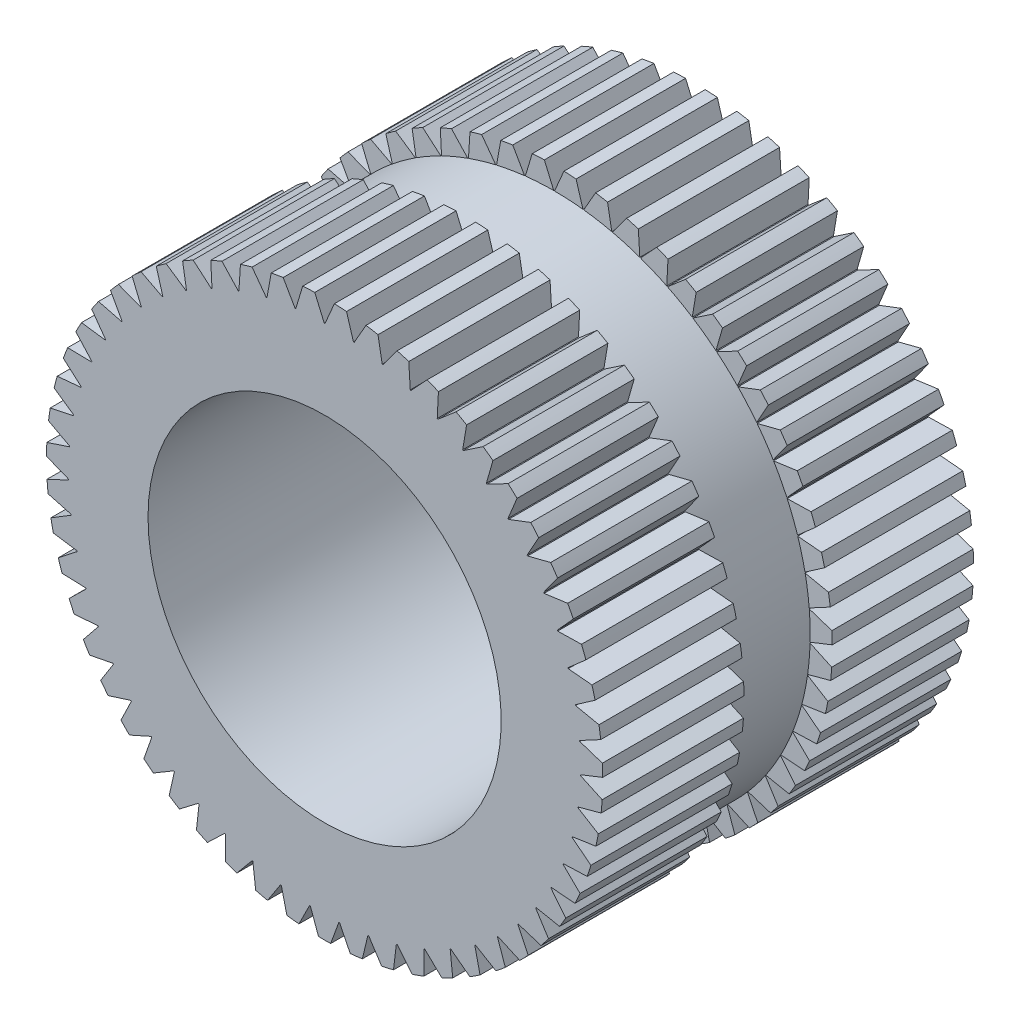
SolidWorks part; units mm, degrees
material "Brass"
ref_plane "Front Plane" through (0, 0, 0) normal (0, 0, 1) x (1, 0, 0)
ref_plane "Top Plane" through (0, 0, 0) normal (0, 1, 0) x (1, 0, 0)
ref_plane "Right Plane" through (0, 0, 0) normal (1, 0, 0) x (0, 0, -1)
ref_plane "Plane1" through (0, 0, 2.1) normal (0, 0, 1) x (1, 0, 0)
sketch "Sketch1" plane through (0, 0, 2.1) normal (0, 0, 1) x (1, 0, 0)
  line L0 (-2.8431, 0.5717) -> (-3.1074, 0.5164)
  line L1 (-3.127, 0.38) -> (-2.889, 0.2525)
  line L2 (-2.8897, 0.2438) -> (-3.146, 0.1588)
  line L3 (-3.1499, 0.0211) -> (-2.8989, -0.0785)
  line L4 (-2.8987, -0.0872) -> (-3.1436, -0.2009)
  line L5 (-3.1318, -0.3381) -> (-2.8711, -0.4084)
  line L6 (-2.8699, -0.417) -> (-3.1002, -0.5579)
  line L7 (-3.0728, -0.6929) -> (-2.8058, -0.733)
  line L8 (-2.8036, -0.7414) -> (-3.0164, -0.9077)
  line L9 (-2.9738, -1.0387) -> (-2.704, -1.0481)
  line L10 (-2.7008, -1.0562) -> (-2.8933, -1.2456)
  line L11 (-2.836, -1.3709) -> (-2.5669, -1.3495)
  line L12 (-2.5628, -1.3572) -> (-2.7324, -1.5673)
  line L13 (-2.6613, -1.6852) -> (-2.3963, -1.6333)
  line L14 (-2.3914, -1.6405) -> (-2.536, -1.8685)
  line L15 (-2.4518, -1.9776) -> (-2.1945, -1.8958)
  line L16 (-2.1888, -1.9024) -> (-2.3064, -2.1454)
  line L17 (-2.2104, -2.2442) -> (-1.9641, -2.1336)
  line L18 (-1.9577, -2.1395) -> (-2.0468, -2.3944)
  line L19 (-1.9402, -2.4816) -> (-1.7081, -2.3436)
  line L20 (-1.7011, -2.3487) -> (-1.7605, -2.6121)
  line L21 (-1.6447, -2.6865) -> (-1.4298, -2.523)
  line L22 (-1.4222, -2.5273) -> (-1.4513, -2.7957)
  line L23 (-1.3277, -2.8565) -> (-1.1329, -2.6696)
  line L24 (-1.1249, -2.6729) -> (-1.1232, -2.943)
  line L25 (-0.9934, -2.9892) -> (-0.8212, -2.7813)
  line L26 (-0.8129, -2.7838) -> (-0.7804, -3.0518)
  line L27 (-0.6462, -3.083) -> (-0.4988, -2.8568)
  line L28 (-0.4902, -2.8583) -> (-0.4274, -3.1209)
  line L29 (-0.2906, -3.1366) -> (-0.1699, -2.895)
  line L30 (-0.1612, -2.8955) -> (-0.0689, -3.1492)
  line L31 (0.0689, -3.1492) -> (0.1612, -2.8955)
  line L32 (0.1699, -2.895) -> (0.2906, -3.1366)
  line L33 (0.4274, -3.1209) -> (0.4902, -2.8583)
  line L34 (0.4988, -2.8568) -> (0.6462, -3.083)
  line L35 (0.7804, -3.0518) -> (0.8129, -2.7838)
  line L36 (0.8212, -2.7813) -> (0.9934, -2.9892)
  line L37 (1.1232, -2.943) -> (1.1249, -2.6729)
  line L38 (1.1329, -2.6696) -> (1.3277, -2.8565)
  line L39 (1.4513, -2.7957) -> (1.4222, -2.5273)
  line L40 (1.4298, -2.523) -> (1.6447, -2.6865)
  line L41 (1.7605, -2.6121) -> (1.7011, -2.3487)
  line L42 (1.7081, -2.3436) -> (1.9402, -2.4816)
  line L43 (2.0468, -2.3944) -> (1.9577, -2.1395)
  line L44 (1.9641, -2.1336) -> (2.2104, -2.2442)
  line L45 (2.3064, -2.1454) -> (2.1888, -1.9024)
  line L46 (2.1945, -1.8958) -> (2.4518, -1.9776)
  line L47 (2.536, -1.8685) -> (2.3914, -1.6405)
  line L48 (2.3963, -1.6333) -> (2.6613, -1.6852)
  line L49 (2.7324, -1.5673) -> (2.5628, -1.3572)
  line L50 (2.5669, -1.3495) -> (2.836, -1.3709)
  line L51 (2.8933, -1.2456) -> (2.7008, -1.0562)
  line L52 (2.704, -1.0481) -> (2.9738, -1.0387)
  line L53 (3.0164, -0.9077) -> (2.8036, -0.7414)
  line L54 (2.8058, -0.733) -> (3.0728, -0.6929)
  line L55 (3.1002, -0.5579) -> (2.8699, -0.417)
  line L56 (2.8711, -0.4084) -> (3.1318, -0.3381)
  line L57 (3.1436, -0.2009) -> (2.8987, -0.0872)
  line L58 (2.8989, -0.0785) -> (3.1499, 0.0211)
  line L59 (3.146, 0.1588) -> (2.8897, 0.2438)
  line L60 (2.889, 0.2525) -> (3.127, 0.38)
  line L61 (3.1074, 0.5164) -> (2.8431, 0.5717)
  line L62 (2.8414, 0.5802) -> (3.0633, 0.734)
  line L63 (3.0283, 0.8672) -> (2.7594, 0.892)
  line L64 (2.7567, 0.9003) -> (2.9597, 1.0784)
  line L65 (2.9097, 1.2067) -> (2.6397, 1.2008)
  line L66 (2.6361, 1.2087) -> (2.8174, 1.4087)
  line L67 (2.7532, 1.5306) -> (2.4857, 1.4938)
  line L68 (2.4812, 1.5013) -> (2.6385, 1.7207)
  line L69 (2.5607, 1.8344) -> (2.2992, 1.7674)
  line L70 (2.2939, 1.7743) -> (2.4251, 2.0103)
  line L71 (2.3349, 2.1144) -> (2.0827, 2.018)
  line L72 (2.0767, 2.0242) -> (2.1802, 2.2736)
  line L73 (2.0787, 2.3667) -> (1.8391, 2.2423)
  line L74 (1.8324, 2.2478) -> (1.9068, 2.5073)
  line L75 (1.7954, 2.5883) -> (1.5715, 2.4373)
  line L76 (1.5642, 2.442) -> (1.6086, 2.7083)
  line L77 (1.4886, 2.7761) -> (1.2834, 2.6005)
  line L78 (1.2756, 2.6044) -> (1.2893, 2.874)
  line L79 (1.1625, 2.9277) -> (0.9786, 2.7299)
  line L80 (0.9705, 2.7328) -> (0.9533, 3.0023)
  line L81 (0.8212, 3.0411) -> (0.6611, 2.8236)
  line L82 (0.6526, 2.8256) -> (0.6049, 3.0914)
  line L83 (0.4692, 3.1149) -> (0.3349, 2.8806)
  line L84 (0.3263, 2.8816) -> (0.2485, 3.1402)
  line L85 (0.111, 3.148) -> (0.0043, 2.9)
  line L86 (-0.0043, 2.9) -> (-0.111, 3.148)
  line L87 (-0.2485, 3.1402) -> (-0.3263, 2.8816)
  line L88 (-0.3349, 2.8806) -> (-0.4692, 3.1149)
  line L89 (-0.6049, 3.0914) -> (-0.6526, 2.8256)
  line L90 (-0.6611, 2.8236) -> (-0.8212, 3.0411)
  line L91 (-0.9533, 3.0023) -> (-0.9705, 2.7328)
  line L92 (-0.9786, 2.7299) -> (-1.1625, 2.9277)
  line L93 (-1.2893, 2.874) -> (-1.2756, 2.6044)
  line L94 (-1.2834, 2.6005) -> (-1.4886, 2.7761)
  line L95 (-1.6086, 2.7083) -> (-1.5642, 2.442)
  line L96 (-1.5715, 2.4373) -> (-1.7954, 2.5883)
  line L97 (-1.9068, 2.5073) -> (-1.8324, 2.2478)
  line L98 (-1.8391, 2.2423) -> (-2.0787, 2.3667)
  line L99 (-2.1802, 2.2736) -> (-2.0767, 2.0242)
  line L100 (-2.0827, 2.018) -> (-2.3349, 2.1144)
  line L101 (-2.4251, 2.0103) -> (-2.2939, 1.7743)
  line L102 (-2.2992, 1.7674) -> (-2.5607, 1.8344)
  line L103 (-2.6385, 1.7207) -> (-2.4812, 1.5013)
  line L104 (-2.4857, 1.4938) -> (-2.7532, 1.5306)
  line L105 (-2.8174, 1.4087) -> (-2.6361, 1.2087)
  line L106 (-2.6397, 1.2008) -> (-2.9097, 1.2067)
  line L107 (-2.9597, 1.0784) -> (-2.7567, 0.9003)
  line L108 (-2.7594, 0.892) -> (-3.0283, 0.8672)
  line L109 (-3.0633, 0.734) -> (-2.8414, 0.5802)
  arc A0 (-2.8414, 0.5802) -> (-2.8431, 0.5717) centre (0, 0) ccw
  arc A1 (-3.1074, 0.5164) -> (-3.127, 0.38) centre (0, 0) ccw
  arc A2 (-2.889, 0.2525) -> (-2.8897, 0.2438) centre (0, 0) ccw
  arc A3 (-3.146, 0.1588) -> (-3.1499, 0.0211) centre (0, 0) ccw
  arc A4 (-2.8989, -0.0785) -> (-2.8987, -0.0872) centre (0, 0) ccw
  arc A5 (-3.1436, -0.2009) -> (-3.1318, -0.3381) centre (0, 0) ccw
  arc A6 (-2.8711, -0.4084) -> (-2.8699, -0.417) centre (0, 0) ccw
  arc A7 (-3.1002, -0.5579) -> (-3.0728, -0.6929) centre (0, 0) ccw
  arc A8 (-2.8058, -0.733) -> (-2.8036, -0.7414) centre (0, 0) ccw
  arc A9 (-3.0164, -0.9077) -> (-2.9738, -1.0387) centre (0, 0) ccw
  arc A10 (-2.704, -1.0481) -> (-2.7008, -1.0562) centre (0, 0) ccw
  arc A11 (-2.8933, -1.2456) -> (-2.836, -1.3709) centre (0, 0) ccw
  arc A12 (-2.5669, -1.3495) -> (-2.5628, -1.3572) centre (0, 0) ccw
  arc A13 (-2.7324, -1.5673) -> (-2.6613, -1.6852) centre (0, 0) ccw
  arc A14 (-2.3963, -1.6333) -> (-2.3914, -1.6405) centre (0, 0) ccw
  arc A15 (-2.536, -1.8685) -> (-2.4518, -1.9776) centre (0, 0) ccw
  arc A16 (-2.1945, -1.8958) -> (-2.1888, -1.9024) centre (0, 0) ccw
  arc A17 (-2.3064, -2.1454) -> (-2.2104, -2.2442) centre (0, 0) ccw
  arc A18 (-1.9641, -2.1336) -> (-1.9577, -2.1395) centre (0, 0) ccw
  arc A19 (-2.0468, -2.3944) -> (-1.9402, -2.4816) centre (0, 0) ccw
  arc A20 (-1.7081, -2.3436) -> (-1.7011, -2.3487) centre (0, 0) ccw
  arc A21 (-1.7605, -2.6121) -> (-1.6447, -2.6865) centre (0, 0) ccw
  arc A22 (-1.4298, -2.523) -> (-1.4222, -2.5273) centre (0, 0) ccw
  arc A23 (-1.4513, -2.7957) -> (-1.3277, -2.8565) centre (0, 0) ccw
  arc A24 (-1.1329, -2.6696) -> (-1.1249, -2.6729) centre (0, 0) ccw
  arc A25 (-1.1232, -2.943) -> (-0.9934, -2.9892) centre (0, 0) ccw
  arc A26 (-0.8212, -2.7813) -> (-0.8129, -2.7838) centre (0, 0) ccw
  arc A27 (-0.7804, -3.0518) -> (-0.6462, -3.083) centre (0, 0) ccw
  arc A28 (-0.4988, -2.8568) -> (-0.4902, -2.8583) centre (0, 0) ccw
  arc A29 (-0.4274, -3.1209) -> (-0.2906, -3.1366) centre (0, 0) ccw
  arc A30 (-0.1699, -2.895) -> (-0.1612, -2.8955) centre (0, 0) ccw
  arc A31 (-0.0689, -3.1492) -> (0.0689, -3.1492) centre (0, 0) ccw
  arc A32 (0.1612, -2.8955) -> (0.1699, -2.895) centre (0, 0) ccw
  arc A33 (0.2906, -3.1366) -> (0.4274, -3.1209) centre (0, 0) ccw
  arc A34 (0.4902, -2.8583) -> (0.4988, -2.8568) centre (0, 0) ccw
  arc A35 (0.6462, -3.083) -> (0.7804, -3.0518) centre (0, 0) ccw
  arc A36 (0.8129, -2.7838) -> (0.8212, -2.7813) centre (0, 0) ccw
  arc A37 (0.9934, -2.9892) -> (1.1232, -2.943) centre (0, 0) ccw
  arc A38 (1.1249, -2.6729) -> (1.1329, -2.6696) centre (0, 0) ccw
  arc A39 (1.3277, -2.8565) -> (1.4513, -2.7957) centre (0, 0) ccw
  arc A40 (1.4222, -2.5273) -> (1.4298, -2.523) centre (0, 0) ccw
  arc A41 (1.6447, -2.6865) -> (1.7605, -2.6121) centre (0, 0) ccw
  arc A42 (1.7011, -2.3487) -> (1.7081, -2.3436) centre (0, 0) ccw
  arc A43 (1.9402, -2.4816) -> (2.0468, -2.3944) centre (0, 0) ccw
  arc A44 (1.9577, -2.1395) -> (1.9641, -2.1336) centre (0, 0) ccw
  arc A45 (2.2104, -2.2442) -> (2.3064, -2.1454) centre (0, 0) ccw
  arc A46 (2.1888, -1.9024) -> (2.1945, -1.8958) centre (0, 0) ccw
  arc A47 (2.4518, -1.9776) -> (2.536, -1.8685) centre (0, 0) ccw
  arc A48 (2.3914, -1.6405) -> (2.3963, -1.6333) centre (0, 0) ccw
  arc A49 (2.6613, -1.6852) -> (2.7324, -1.5673) centre (0, 0) ccw
  arc A50 (2.5628, -1.3572) -> (2.5669, -1.3495) centre (0, 0) ccw
  arc A51 (2.836, -1.3709) -> (2.8933, -1.2456) centre (0, 0) ccw
  arc A52 (2.7008, -1.0562) -> (2.704, -1.0481) centre (0, 0) ccw
  arc A53 (2.9738, -1.0387) -> (3.0164, -0.9077) centre (0, 0) ccw
  arc A54 (2.8036, -0.7414) -> (2.8058, -0.733) centre (0, 0) ccw
  arc A55 (3.0728, -0.6929) -> (3.1002, -0.5579) centre (0, 0) ccw
  arc A56 (2.8699, -0.417) -> (2.8711, -0.4084) centre (0, 0) ccw
  arc A57 (3.1318, -0.3381) -> (3.1436, -0.2009) centre (0, 0) ccw
  arc A58 (2.8987, -0.0872) -> (2.8989, -0.0785) centre (0, 0) ccw
  arc A59 (3.1499, 0.0211) -> (3.146, 0.1588) centre (0, 0) ccw
  arc A60 (2.8897, 0.2438) -> (2.889, 0.2525) centre (0, 0) ccw
  arc A61 (3.127, 0.38) -> (3.1074, 0.5164) centre (0, 0) ccw
  arc A62 (2.8431, 0.5717) -> (2.8414, 0.5802) centre (0, 0) ccw
  arc A63 (3.0633, 0.734) -> (3.0283, 0.8672) centre (0, 0) ccw
  arc A64 (2.7594, 0.892) -> (2.7567, 0.9003) centre (0, 0) ccw
  arc A65 (2.9597, 1.0784) -> (2.9097, 1.2067) centre (0, 0) ccw
  arc A66 (2.6397, 1.2008) -> (2.6361, 1.2087) centre (0, 0) ccw
  arc A67 (2.8174, 1.4087) -> (2.7532, 1.5306) centre (0, 0) ccw
  arc A68 (2.4857, 1.4938) -> (2.4812, 1.5013) centre (0, 0) ccw
  arc A69 (2.6385, 1.7207) -> (2.5607, 1.8344) centre (0, 0) ccw
  arc A70 (2.2992, 1.7674) -> (2.2939, 1.7743) centre (0, 0) ccw
  arc A71 (2.4251, 2.0103) -> (2.3349, 2.1144) centre (0, 0) ccw
  arc A72 (2.0827, 2.018) -> (2.0767, 2.0242) centre (0, 0) ccw
  arc A73 (2.1802, 2.2736) -> (2.0787, 2.3667) centre (0, 0) ccw
  arc A74 (1.8391, 2.2423) -> (1.8324, 2.2478) centre (0, 0) ccw
  arc A75 (1.9068, 2.5073) -> (1.7954, 2.5883) centre (0, 0) ccw
  arc A76 (1.5715, 2.4373) -> (1.5642, 2.442) centre (0, 0) ccw
  arc A77 (1.6086, 2.7083) -> (1.4886, 2.7761) centre (0, 0) ccw
  arc A78 (1.2834, 2.6005) -> (1.2756, 2.6044) centre (0, 0) ccw
  arc A79 (1.2893, 2.874) -> (1.1625, 2.9277) centre (0, 0) ccw
  arc A80 (0.9786, 2.7299) -> (0.9705, 2.7328) centre (0, 0) ccw
  arc A81 (0.9533, 3.0023) -> (0.8212, 3.0411) centre (0, 0) ccw
  arc A82 (0.6611, 2.8236) -> (0.6526, 2.8256) centre (0, 0) ccw
  arc A83 (0.6049, 3.0914) -> (0.4692, 3.1149) centre (0, 0) ccw
  arc A84 (0.3349, 2.8806) -> (0.3263, 2.8816) centre (0, 0) ccw
  arc A85 (0.2485, 3.1402) -> (0.111, 3.148) centre (0, 0) ccw
  arc A86 (0.0043, 2.9) -> (-0.0043, 2.9) centre (0, 0) ccw
  arc A87 (-0.111, 3.148) -> (-0.2485, 3.1402) centre (0, 0) ccw
  arc A88 (-0.3263, 2.8816) -> (-0.3349, 2.8806) centre (0, 0) ccw
  arc A89 (-0.4692, 3.1149) -> (-0.6049, 3.0914) centre (0, 0) ccw
  arc A90 (-0.6526, 2.8256) -> (-0.6611, 2.8236) centre (0, 0) ccw
  arc A91 (-0.8212, 3.0411) -> (-0.9533, 3.0023) centre (0, 0) ccw
  arc A92 (-0.9705, 2.7328) -> (-0.9786, 2.7299) centre (0, 0) ccw
  arc A93 (-1.1625, 2.9277) -> (-1.2893, 2.874) centre (0, 0) ccw
  arc A94 (-1.2756, 2.6044) -> (-1.2834, 2.6005) centre (0, 0) ccw
  arc A95 (-1.4886, 2.7761) -> (-1.6086, 2.7083) centre (0, 0) ccw
  arc A96 (-1.5642, 2.442) -> (-1.5715, 2.4373) centre (0, 0) ccw
  arc A97 (-1.7954, 2.5883) -> (-1.9068, 2.5073) centre (0, 0) ccw
  arc A98 (-1.8324, 2.2478) -> (-1.8391, 2.2423) centre (0, 0) ccw
  arc A99 (-2.0787, 2.3667) -> (-2.1802, 2.2736) centre (0, 0) ccw
  arc A100 (-2.0767, 2.0242) -> (-2.0827, 2.018) centre (0, 0) ccw
  arc A101 (-2.3349, 2.1144) -> (-2.4251, 2.0103) centre (0, 0) ccw
  arc A102 (-2.2939, 1.7743) -> (-2.2992, 1.7674) centre (0, 0) ccw
  arc A103 (-2.5607, 1.8344) -> (-2.6385, 1.7207) centre (0, 0) ccw
  arc A104 (-2.4812, 1.5013) -> (-2.4857, 1.4938) centre (0, 0) ccw
  arc A105 (-2.7532, 1.5306) -> (-2.8174, 1.4087) centre (0, 0) ccw
  arc A106 (-2.6361, 1.2087) -> (-2.6397, 1.2008) centre (0, 0) ccw
  arc A107 (-2.9097, 1.2067) -> (-2.9597, 1.0784) centre (0, 0) ccw
  arc A108 (-2.7567, 0.9003) -> (-2.7594, 0.892) centre (0, 0) ccw
  arc A109 (-3.0283, 0.8672) -> (-3.0633, 0.734) centre (0, 0) ccw
extrude "Boss-Extrude1" add sketch "Sketch1" against normal blind 1.6
sketch "Sketch2" plane through (0, 0, 0.5) normal (0, 0, -1) x (-1, 0, 0)
  circle A0 centre (0, 0) radius 2.9
extrude "Boss-Extrude2" add sketch "Sketch2" along normal blind 1
sketch "Sketch3" plane through (0, 0, -0.5) normal (0, 0, -1) x (-1, 0, 0)
  line L0 (2.6397, 1.2008) -> (2.9097, 1.2067)
  line L1 (2.9597, 1.0784) -> (2.7567, 0.9003)
  line L2 (2.7594, 0.892) -> (3.0283, 0.8672)
  line L3 (3.0633, 0.734) -> (2.8414, 0.5802)
  line L4 (2.8431, 0.5717) -> (3.1074, 0.5164)
  line L5 (3.127, 0.38) -> (2.889, 0.2525)
  line L6 (2.8897, 0.2438) -> (3.146, 0.1588)
  line L7 (3.1499, 0.0211) -> (2.8989, -0.0785)
  line L8 (2.8987, -0.0872) -> (3.1436, -0.2009)
  line L9 (3.1318, -0.3381) -> (2.8711, -0.4084)
  line L10 (2.8699, -0.417) -> (3.1002, -0.5579)
  line L11 (3.0728, -0.6929) -> (2.8058, -0.733)
  line L12 (2.8036, -0.7414) -> (3.0164, -0.9077)
  line L13 (2.9738, -1.0387) -> (2.704, -1.0481)
  line L14 (2.7008, -1.0562) -> (2.8933, -1.2456)
  line L15 (2.836, -1.3709) -> (2.5669, -1.3495)
  line L16 (2.5628, -1.3572) -> (2.7324, -1.5673)
  line L17 (2.6613, -1.6852) -> (2.3963, -1.6333)
  line L18 (2.3914, -1.6405) -> (2.536, -1.8685)
  line L19 (2.4518, -1.9776) -> (2.1945, -1.8958)
  line L20 (2.1888, -1.9024) -> (2.3064, -2.1454)
  line L21 (2.2104, -2.2442) -> (1.9641, -2.1336)
  line L22 (1.9577, -2.1395) -> (2.0468, -2.3944)
  line L23 (1.9402, -2.4816) -> (1.7081, -2.3436)
  line L24 (1.7011, -2.3487) -> (1.7605, -2.6121)
  line L25 (1.6447, -2.6865) -> (1.4298, -2.523)
  line L26 (1.4222, -2.5273) -> (1.4513, -2.7957)
  line L27 (1.3277, -2.8565) -> (1.1329, -2.6696)
  line L28 (1.1249, -2.6729) -> (1.1232, -2.943)
  line L29 (0.9934, -2.9892) -> (0.8212, -2.7813)
  line L30 (0.8129, -2.7838) -> (0.7804, -3.0518)
  line L31 (0.6462, -3.083) -> (0.4988, -2.8568)
  line L32 (0.4902, -2.8583) -> (0.4274, -3.1209)
  line L33 (0.2906, -3.1366) -> (0.1699, -2.895)
  line L34 (0.1612, -2.8955) -> (0.0689, -3.1492)
  line L35 (-0.0689, -3.1492) -> (-0.1612, -2.8955)
  line L36 (-0.1699, -2.895) -> (-0.2906, -3.1366)
  line L37 (-0.4274, -3.1209) -> (-0.4902, -2.8583)
  line L38 (-0.4988, -2.8568) -> (-0.6462, -3.083)
  line L39 (-0.7804, -3.0518) -> (-0.8129, -2.7838)
  line L40 (-0.8212, -2.7813) -> (-0.9934, -2.9892)
  line L41 (-1.1232, -2.943) -> (-1.1249, -2.6729)
  line L42 (-1.1329, -2.6696) -> (-1.3277, -2.8565)
  line L43 (-1.4513, -2.7957) -> (-1.4222, -2.5273)
  line L44 (-1.4298, -2.523) -> (-1.6447, -2.6865)
  line L45 (-1.7605, -2.6121) -> (-1.7011, -2.3487)
  line L46 (-1.7081, -2.3436) -> (-1.9402, -2.4816)
  line L47 (-2.0468, -2.3944) -> (-1.9577, -2.1395)
  line L48 (-1.9641, -2.1336) -> (-2.2104, -2.2442)
  line L49 (-2.3064, -2.1454) -> (-2.1888, -1.9024)
  line L50 (-2.1945, -1.8958) -> (-2.4518, -1.9776)
  line L51 (-2.536, -1.8685) -> (-2.3914, -1.6405)
  line L52 (-2.3963, -1.6333) -> (-2.6613, -1.6852)
  line L53 (-2.7324, -1.5673) -> (-2.5628, -1.3572)
  line L54 (-2.5669, -1.3495) -> (-2.836, -1.3709)
  line L55 (-2.8933, -1.2456) -> (-2.7008, -1.0562)
  line L56 (-2.704, -1.0481) -> (-2.9738, -1.0387)
  line L57 (-3.0164, -0.9077) -> (-2.8036, -0.7414)
  line L58 (-2.8058, -0.733) -> (-3.0728, -0.6929)
  line L59 (-3.1002, -0.5579) -> (-2.8699, -0.417)
  line L60 (-2.8711, -0.4084) -> (-3.1318, -0.3381)
  line L61 (-3.1436, -0.2009) -> (-2.8987, -0.0872)
  line L62 (-2.8989, -0.0785) -> (-3.1499, 0.0211)
  line L63 (-3.146, 0.1588) -> (-2.8897, 0.2438)
  line L64 (-2.889, 0.2525) -> (-3.127, 0.38)
  line L65 (-3.1074, 0.5164) -> (-2.8431, 0.5717)
  line L66 (-2.8414, 0.5802) -> (-3.0633, 0.734)
  line L67 (-3.0283, 0.8672) -> (-2.7594, 0.892)
  line L68 (-2.7567, 0.9003) -> (-2.9597, 1.0784)
  line L69 (-2.9097, 1.2067) -> (-2.6397, 1.2008)
  line L70 (-2.6361, 1.2087) -> (-2.8174, 1.4087)
  line L71 (-2.7532, 1.5306) -> (-2.4857, 1.4938)
  line L72 (-2.4812, 1.5013) -> (-2.6385, 1.7207)
  line L73 (-2.5607, 1.8344) -> (-2.2992, 1.7674)
  line L74 (-2.2939, 1.7743) -> (-2.4251, 2.0103)
  line L75 (-2.3349, 2.1144) -> (-2.0827, 2.018)
  line L76 (-2.0767, 2.0242) -> (-2.1802, 2.2736)
  line L77 (-2.0787, 2.3667) -> (-1.8391, 2.2423)
  line L78 (-1.8324, 2.2478) -> (-1.9068, 2.5073)
  line L79 (-1.7954, 2.5883) -> (-1.5715, 2.4373)
  line L80 (-1.5642, 2.442) -> (-1.6086, 2.7083)
  line L81 (-1.4886, 2.7761) -> (-1.2834, 2.6005)
  line L82 (-1.2756, 2.6044) -> (-1.2893, 2.874)
  line L83 (-1.1625, 2.9277) -> (-0.9786, 2.7299)
  line L84 (-0.9705, 2.7328) -> (-0.9533, 3.0023)
  line L85 (-0.8212, 3.0411) -> (-0.6611, 2.8236)
  line L86 (-0.6526, 2.8256) -> (-0.6049, 3.0914)
  line L87 (-0.4692, 3.1149) -> (-0.3349, 2.8806)
  line L88 (-0.3263, 2.8816) -> (-0.2485, 3.1402)
  line L89 (-0.111, 3.148) -> (-0.0043, 2.9)
  line L90 (0.0043, 2.9) -> (0.111, 3.148)
  line L91 (0.2485, 3.1402) -> (0.3263, 2.8816)
  line L92 (0.3349, 2.8806) -> (0.4692, 3.1149)
  line L93 (0.6049, 3.0914) -> (0.6526, 2.8256)
  line L94 (0.6611, 2.8236) -> (0.8212, 3.0411)
  line L95 (0.9533, 3.0023) -> (0.9705, 2.7328)
  line L96 (0.9786, 2.7299) -> (1.1625, 2.9277)
  line L97 (1.2893, 2.874) -> (1.2756, 2.6044)
  line L98 (1.2834, 2.6005) -> (1.4886, 2.7761)
  line L99 (1.6086, 2.7083) -> (1.5642, 2.442)
  line L100 (1.5715, 2.4373) -> (1.7954, 2.5883)
  line L101 (1.9068, 2.5073) -> (1.8324, 2.2478)
  line L102 (1.8391, 2.2423) -> (2.0787, 2.3667)
  line L103 (2.1802, 2.2736) -> (2.0767, 2.0242)
  line L104 (2.0827, 2.018) -> (2.3349, 2.1144)
  line L105 (2.4251, 2.0103) -> (2.2939, 1.7743)
  line L106 (2.2992, 1.7674) -> (2.5607, 1.8344)
  line L107 (2.6385, 1.7207) -> (2.4812, 1.5013)
  line L108 (2.4857, 1.4938) -> (2.7532, 1.5306)
  line L109 (2.8174, 1.4087) -> (2.6361, 1.2087)
  arc A0 (2.6361, 1.2087) -> (2.6397, 1.2008) centre (0, 0) cw
  arc A1 (2.9097, 1.2067) -> (2.9597, 1.0784) centre (0, 0) cw
  arc A2 (2.7567, 0.9003) -> (2.7594, 0.892) centre (0, 0) cw
  arc A3 (3.0283, 0.8672) -> (3.0633, 0.734) centre (0, 0) cw
  arc A4 (2.8414, 0.5802) -> (2.8431, 0.5717) centre (0, 0) cw
  arc A5 (3.1074, 0.5164) -> (3.127, 0.38) centre (0, 0) cw
  arc A6 (2.889, 0.2525) -> (2.8897, 0.2438) centre (0, 0) cw
  arc A7 (3.146, 0.1588) -> (3.1499, 0.0211) centre (0, 0) cw
  arc A8 (2.8989, -0.0785) -> (2.8987, -0.0872) centre (0, 0) cw
  arc A9 (3.1436, -0.2009) -> (3.1318, -0.3381) centre (0, 0) cw
  arc A10 (2.8711, -0.4084) -> (2.8699, -0.417) centre (0, 0) cw
  arc A11 (3.1002, -0.5579) -> (3.0728, -0.6929) centre (0, 0) cw
  arc A12 (2.8058, -0.733) -> (2.8036, -0.7414) centre (0, 0) cw
  arc A13 (3.0164, -0.9077) -> (2.9738, -1.0387) centre (0, 0) cw
  arc A14 (2.704, -1.0481) -> (2.7008, -1.0562) centre (0, 0) cw
  arc A15 (2.8933, -1.2456) -> (2.836, -1.3709) centre (0, 0) cw
  arc A16 (2.5669, -1.3495) -> (2.5628, -1.3572) centre (0, 0) cw
  arc A17 (2.7324, -1.5673) -> (2.6613, -1.6852) centre (0, 0) cw
  arc A18 (2.3963, -1.6333) -> (2.3914, -1.6405) centre (0, 0) cw
  arc A19 (2.536, -1.8685) -> (2.4518, -1.9776) centre (0, 0) cw
  arc A20 (2.1945, -1.8958) -> (2.1888, -1.9024) centre (0, 0) cw
  arc A21 (2.3064, -2.1454) -> (2.2104, -2.2442) centre (0, 0) cw
  arc A22 (1.9641, -2.1336) -> (1.9577, -2.1395) centre (0, 0) cw
  arc A23 (2.0468, -2.3944) -> (1.9402, -2.4816) centre (0, 0) cw
  arc A24 (1.7081, -2.3436) -> (1.7011, -2.3487) centre (0, 0) cw
  arc A25 (1.7605, -2.6121) -> (1.6447, -2.6865) centre (0, 0) cw
  arc A26 (1.4298, -2.523) -> (1.4222, -2.5273) centre (0, 0) cw
  arc A27 (1.4513, -2.7957) -> (1.3277, -2.8565) centre (0, 0) cw
  arc A28 (1.1329, -2.6696) -> (1.1249, -2.6729) centre (0, 0) cw
  arc A29 (1.1232, -2.943) -> (0.9934, -2.9892) centre (0, 0) cw
  arc A30 (0.8212, -2.7813) -> (0.8129, -2.7838) centre (0, 0) cw
  arc A31 (0.7804, -3.0518) -> (0.6462, -3.083) centre (0, 0) cw
  arc A32 (0.4988, -2.8568) -> (0.4902, -2.8583) centre (0, 0) cw
  arc A33 (0.4274, -3.1209) -> (0.2906, -3.1366) centre (0, 0) cw
  arc A34 (0.1699, -2.895) -> (0.1612, -2.8955) centre (0, 0) cw
  arc A35 (0.0689, -3.1492) -> (-0.0689, -3.1492) centre (0, 0) cw
  arc A36 (-0.1612, -2.8955) -> (-0.1699, -2.895) centre (0, 0) cw
  arc A37 (-0.2906, -3.1366) -> (-0.4274, -3.1209) centre (0, 0) cw
  arc A38 (-0.4902, -2.8583) -> (-0.4988, -2.8568) centre (0, 0) cw
  arc A39 (-0.6462, -3.083) -> (-0.7804, -3.0518) centre (0, 0) cw
  arc A40 (-0.8129, -2.7838) -> (-0.8212, -2.7813) centre (0, 0) cw
  arc A41 (-0.9934, -2.9892) -> (-1.1232, -2.943) centre (0, 0) cw
  arc A42 (-1.1249, -2.6729) -> (-1.1329, -2.6696) centre (0, 0) cw
  arc A43 (-1.3277, -2.8565) -> (-1.4513, -2.7957) centre (0, 0) cw
  arc A44 (-1.4222, -2.5273) -> (-1.4298, -2.523) centre (0, 0) cw
  arc A45 (-1.6447, -2.6865) -> (-1.7605, -2.6121) centre (0, 0) cw
  arc A46 (-1.7011, -2.3487) -> (-1.7081, -2.3436) centre (0, 0) cw
  arc A47 (-1.9402, -2.4816) -> (-2.0468, -2.3944) centre (0, 0) cw
  arc A48 (-1.9577, -2.1395) -> (-1.9641, -2.1336) centre (0, 0) cw
  arc A49 (-2.2104, -2.2442) -> (-2.3064, -2.1454) centre (0, 0) cw
  arc A50 (-2.1888, -1.9024) -> (-2.1945, -1.8958) centre (0, 0) cw
  arc A51 (-2.4518, -1.9776) -> (-2.536, -1.8685) centre (0, 0) cw
  arc A52 (-2.3914, -1.6405) -> (-2.3963, -1.6333) centre (0, 0) cw
  arc A53 (-2.6613, -1.6852) -> (-2.7324, -1.5673) centre (0, 0) cw
  arc A54 (-2.5628, -1.3572) -> (-2.5669, -1.3495) centre (0, 0) cw
  arc A55 (-2.836, -1.3709) -> (-2.8933, -1.2456) centre (0, 0) cw
  arc A56 (-2.7008, -1.0562) -> (-2.704, -1.0481) centre (0, 0) cw
  arc A57 (-2.9738, -1.0387) -> (-3.0164, -0.9077) centre (0, 0) cw
  arc A58 (-2.8036, -0.7414) -> (-2.8058, -0.733) centre (0, 0) cw
  arc A59 (-3.0728, -0.6929) -> (-3.1002, -0.5579) centre (0, 0) cw
  arc A60 (-2.8699, -0.417) -> (-2.8711, -0.4084) centre (0, 0) cw
  arc A61 (-3.1318, -0.3381) -> (-3.1436, -0.2009) centre (0, 0) cw
  arc A62 (-2.8987, -0.0872) -> (-2.8989, -0.0785) centre (0, 0) cw
  arc A63 (-3.1499, 0.0211) -> (-3.146, 0.1588) centre (0, 0) cw
  arc A64 (-2.8897, 0.2438) -> (-2.889, 0.2525) centre (0, 0) cw
  arc A65 (-3.127, 0.38) -> (-3.1074, 0.5164) centre (0, 0) cw
  arc A66 (-2.8431, 0.5717) -> (-2.8414, 0.5802) centre (0, 0) cw
  arc A67 (-3.0633, 0.734) -> (-3.0283, 0.8672) centre (0, 0) cw
  arc A68 (-2.7594, 0.892) -> (-2.7567, 0.9003) centre (0, 0) cw
  arc A69 (-2.9597, 1.0784) -> (-2.9097, 1.2067) centre (0, 0) cw
  arc A70 (-2.6397, 1.2008) -> (-2.6361, 1.2087) centre (0, 0) cw
  arc A71 (-2.8174, 1.4087) -> (-2.7532, 1.5306) centre (0, 0) cw
  arc A72 (-2.4857, 1.4938) -> (-2.4812, 1.5013) centre (0, 0) cw
  arc A73 (-2.6385, 1.7207) -> (-2.5607, 1.8344) centre (0, 0) cw
  arc A74 (-2.2992, 1.7674) -> (-2.2939, 1.7743) centre (0, 0) cw
  arc A75 (-2.4251, 2.0103) -> (-2.3349, 2.1144) centre (0, 0) cw
  arc A76 (-2.0827, 2.018) -> (-2.0767, 2.0242) centre (0, 0) cw
  arc A77 (-2.1802, 2.2736) -> (-2.0787, 2.3667) centre (0, 0) cw
  arc A78 (-1.8391, 2.2423) -> (-1.8324, 2.2478) centre (0, 0) cw
  arc A79 (-1.9068, 2.5073) -> (-1.7954, 2.5883) centre (0, 0) cw
  arc A80 (-1.5715, 2.4373) -> (-1.5642, 2.442) centre (0, 0) cw
  arc A81 (-1.6086, 2.7083) -> (-1.4886, 2.7761) centre (0, 0) cw
  arc A82 (-1.2834, 2.6005) -> (-1.2756, 2.6044) centre (0, 0) cw
  arc A83 (-1.2893, 2.874) -> (-1.1625, 2.9277) centre (0, 0) cw
  arc A84 (-0.9786, 2.7299) -> (-0.9705, 2.7328) centre (0, 0) cw
  arc A85 (-0.9533, 3.0023) -> (-0.8212, 3.0411) centre (0, 0) cw
  arc A86 (-0.6611, 2.8236) -> (-0.6526, 2.8256) centre (0, 0) cw
  arc A87 (-0.6049, 3.0914) -> (-0.4692, 3.1149) centre (0, 0) cw
  arc A88 (-0.3349, 2.8806) -> (-0.3263, 2.8816) centre (0, 0) cw
  arc A89 (-0.2485, 3.1402) -> (-0.111, 3.148) centre (0, 0) cw
  arc A90 (-0.0043, 2.9) -> (0.0043, 2.9) centre (0, 0) cw
  arc A91 (0.111, 3.148) -> (0.2485, 3.1402) centre (0, 0) cw
  arc A92 (0.3263, 2.8816) -> (0.3349, 2.8806) centre (0, 0) cw
  arc A93 (0.4692, 3.1149) -> (0.6049, 3.0914) centre (0, 0) cw
  arc A94 (0.6526, 2.8256) -> (0.6611, 2.8236) centre (0, 0) cw
  arc A95 (0.8212, 3.0411) -> (0.9533, 3.0023) centre (0, 0) cw
  arc A96 (0.9705, 2.7328) -> (0.9786, 2.7299) centre (0, 0) cw
  arc A97 (1.1625, 2.9277) -> (1.2893, 2.874) centre (0, 0) cw
  arc A98 (1.2756, 2.6044) -> (1.2834, 2.6005) centre (0, 0) cw
  arc A99 (1.4886, 2.7761) -> (1.6086, 2.7083) centre (0, 0) cw
  arc A100 (1.5642, 2.442) -> (1.5715, 2.4373) centre (0, 0) cw
  arc A101 (1.7954, 2.5883) -> (1.9068, 2.5073) centre (0, 0) cw
  arc A102 (1.8324, 2.2478) -> (1.8391, 2.2423) centre (0, 0) cw
  arc A103 (2.0787, 2.3667) -> (2.1802, 2.2736) centre (0, 0) cw
  arc A104 (2.0767, 2.0242) -> (2.0827, 2.018) centre (0, 0) cw
  arc A105 (2.3349, 2.1144) -> (2.4251, 2.0103) centre (0, 0) cw
  arc A106 (2.2939, 1.7743) -> (2.2992, 1.7674) centre (0, 0) cw
  arc A107 (2.5607, 1.8344) -> (2.6385, 1.7207) centre (0, 0) cw
  arc A108 (2.4812, 1.5013) -> (2.4857, 1.4938) centre (0, 0) cw
  arc A109 (2.7532, 1.5306) -> (2.8174, 1.4087) centre (0, 0) cw
extrude "Boss-Extrude3" add sketch "Sketch3" along normal blind 1.6
hole_wizard "Ø4.0 (4) Diameter Hole1" positions "Sketch5" profile "Sketch4" hole size "Ø4.0" standard "ANSI Metric"
sketch "Sketch5" plane through (0, 0, -2.1) normal (0, 0, -1) x (-1, 0, 0)
  point P0 (0, 0)
sketch "Sketch4" plane through (0, 0, -2.1) normal (1, 0, 0) x (0, 1, 0)
  line L0 (0, 0) -> (0, 4.2)
  line L1 (0, 4.2) -> (2, 4.2)
  line L2 (2, 4.2) -> (2, 0)
  line L5 (2, 0) -> (0, 0)
  line L11 (0, -6.35) -> (0, 107.95) construction
  dimension "Thru Hole Dia." = 4
  dimension "Thru Hole Depth" = 4.2
